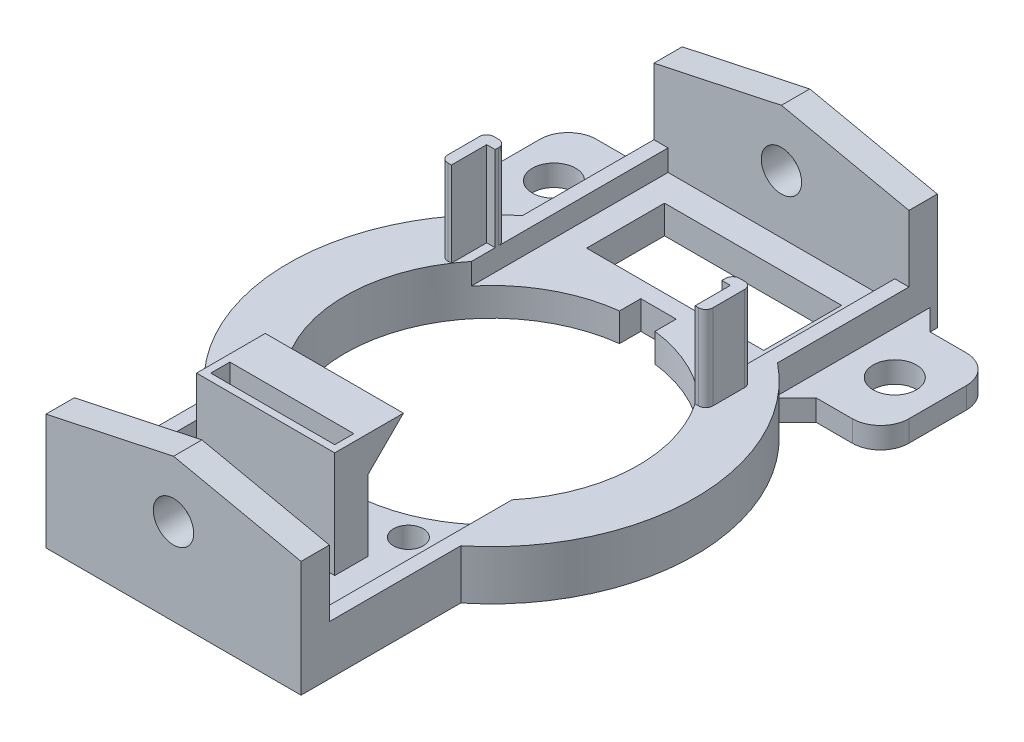
SolidWorks part; units mm, degrees
ref_plane "Front Plane" through (0, 0, 0) normal (0, 0, 1) x (1, 0, 0)
ref_plane "Top Plane" through (0, 0, 0) normal (0, 1, 0) x (1, 0, 0)
ref_plane "Right Plane" through (0, 0, 0) normal (1, 0, 0) x (0, 0, -1)
sketch "Sketch1" plane through (0, 0, 0) normal (0, 0, 1) x (1, 0, 0)
  line L3 (-18, 114.7896) -> (0, 114.7896)
  line L4 (0, 114.7896) -> (18, 114.7896)
  line L7 (0, 118.6383) -> (-38.0273, 110.5073) construction
  line L9 (38.0273, 110.5073) -> (0, 118.6383) construction
  line L11 (18, 114.7896) -> (18, 121.7896)
  line L12 (18, 121.7896) -> (16, 121.7896)
  line L13 (16, 121.7896) -> (16, 118.7896)
  line L14 (16, 118.7896) -> (-16, 118.7896)
  line L15 (-16, 118.7896) -> (-16, 121.7896)
  line L16 (-16, 121.7896) -> (-18, 121.7896)
  line L17 (-18, 121.7896) -> (-18, 114.7896)
  point P15 (0, 118.7896)
  dimension "D1" = 32
  dimension "D2" = 2
  dimension "D3" = 3
  dimension "D4" = 4
extrude "Boss-Extrude1" add sketch "Sketch1" along normal up to surface (89.8 mm away)
sketch "Sketch2" plane through (0, 114.7896, 0) normal (0, -1, 0) x (1, 0, 0)
  line L0 (18, 89.8) -> (18, 0) construction
  line L5 (-14, 54.9) -> (14, 54.9)
  line L6 (-14, 54.9) -> (-14, 34.9)
  line L7 (-14, 34.9) -> (14, 34.9)
  line L8 (14, 54.9) -> (14, 34.9)
  point P4 (0, 34.9)
  point P8 (18, 44.9)
  point P9 (14, 44.9)
  dimension "D1" = 4
  dimension "D2" = 20
extrude "Cut-Extrude1" [suppressed] cut sketch "Sketch2" against normal up to next
sketch "Sketch3" plane through (-18, 0, 0) normal (-1, 0, 0) x (0, 0, 1)
  line L0 (89.8, 121.7896) -> (0, 121.7896) construction
  line L1 (40.65, 118.7896) -> (49.15, 118.7896)
  line L2 (40.65, 118.7896) -> (40.65, 121.7896)
  line L3 (40.65, 121.7896) -> (49.15, 121.7896)
  line L4 (49.15, 118.7896) -> (49.15, 121.7896)
  line L5 (89.8, 118.7896) -> (0, 118.7896) construction
  point P9 (44.9, 121.7896)
  point P10 (44.9, 121.7896)
  dimension "D1" = 8.5
extrude "Cut-Extrude2" [suppressed] cut sketch "Sketch3" against normal through all
sketch "Sketch4" plane through (0, 118.7896, 0) normal (0, 1, 0) x (1, 0, 0)
  circle A0 centre (7.75, -23.25) radius 2.1 construction
  circle A4 centre (-7.75, -23.25) radius 2.1 construction
  circle A5 centre (7.75, -23.25) radius 2.1
  circle A6 centre (-7.75, -23.25) radius 2.1
extrude "Cut-Extrude3" [suppressed] cut sketch "Sketch4" against normal through all
ref_plane "Plane2" through (0, 0, 44.9) normal (0, 0, -1) x (-1, 0, 0)
sketch "Sketch5" plane through (0, 0, 0) normal (0, 0, 1) x (1, 0, 0)
  line L0 (-18, 114.7896) -> (-18, 131.1512)
  line L1 (-56.4, 122.9405) -> (0, 135) construction
  line L2 (-18, 131.1512) -> (0, 135)
  line L3 (0, 135) -> (18, 131.1512)
  line L4 (0, 135) -> (56.4, 122.9405) construction
  line L5 (18, 131.1512) -> (18, 114.7896)
  line L6 (18, 114.7896) -> (-18, 114.7896)
  line L7 (0.6273, 134.8659) -> (54.0273, 123.4479) construction
  line L8 (-54.0273, 123.4479) -> (-0.6273, 134.8659) construction
  circle A0 centre (0, 127) radius 2.85
  dimension "D1" = 5.7
  dimension "D2" = 8
extrude "Boss-Extrude2" add sketch "Sketch5" along normal blind 4
mirror "Mirror1" about plane through (0, 0, 44.9) normal (0, 0, -1) of "Boss-Extrude2"
sketch "Sketch6" plane through (0, 118.7896, 0) normal (0, 1, 0) x (1, 0, 0)
  line L1 (12.5, -19) -> (-12.5, -19)
  line L2 (12.5, -19) -> (12.5, -8)
  line L3 (12.5, -8) -> (-12.5, -8)
  line L4 (-12.5, -19) -> (-12.5, -8)
  point P4 (0, -8)
  dimension "D1" = 11
  dimension "D2" = 25
  dimension "D3" = 8
extrude "Cut-Extrude4" cut sketch "Sketch6" against normal through all
sketch "Sketch8" plane through (0, 118.7896, 0) normal (0, 1, 0) x (1, 0, 0)
  line L0 (16, -85.8) -> (-16, -85.8) construction
  line L1 (8.75, -75.8) -> (-8.75, -75.8)
  line L2 (8.75, -75.8) -> (8.75, -73.1)
  line L3 (8.75, -73.1) -> (-8.75, -73.1)
  line L4 (-8.75, -75.8) -> (-8.75, -73.1)
  line L5 (0, -89.8) -> (53.4, -89.8) construction
  line L6 (9.75, -72.1) -> (-9.75, -72.1)
  line L7 (-9.75, -76.8) -> (-9.75, -72.1)
  line L8 (9.75, -76.8) -> (-9.75, -76.8)
  line L9 (9.75, -76.8) -> (9.75, -72.1)
  point P6 (0, -85.8)
  point P7 (0, -75.8)
  dimension "D1" = 13
  dimension "D2" = 2.7
  dimension "D3" = 17.5
  dimension "D4" = 1
extrude "Boss-Extrude3" add sketch "Sketch8" along normal blind 15
sketch "Sketch9" plane through (-9.75, 0, 0) normal (-1, 0, 0) x (0, 0, 1)
  line L0 (72.1, 128.7896) -> (67.1, 133.7896)
  line L1 (72.1, 133.7896) -> (72.1, 118.7896) construction
  line L2 (67.1, 133.7896) -> (72.1, 133.7896)
  line L3 (72.1, 133.7896) -> (72.1, 128.7896)
  dimension "D1" = 5
  dimension "D2" = 45
extrude "Boss-Extrude4" add sketch "Sketch9" against normal up to surface (19.5 mm away) up to face at (9.75, 126.2896, 74.45)
sketch "Sketch13" plane through (0, 118.7896, 0) normal (0, 1, 0) x (1, 0, 0)
  line L4 (-8.75, -75.8) -> (8.75, -75.8)
  line L5 (8.75, -75.8) -> (8.75, -73.1)
  line L6 (8.75, -73.1) -> (-8.75, -73.1)
  line L7 (-8.75, -73.1) -> (-8.75, -75.8)
  line L8 (-8.75, -75.8) -> (8.75, -75.8)
  line L9 (8.75, -75.8) -> (8.75, -73.1)
  line L10 (8.75, -73.1) -> (-8.75, -73.1)
  line L11 (-8.75, -73.1) -> (-8.75, -75.8)
  dimension "D1" = 0
extrude "Cut-Extrude5" cut sketch "Sketch13" against normal through all
sketch "Sketch10" [suppressed] plane through (0, 121.7896, 0) normal (0, 1, 0) x (1, 0, 0)
  line L1 (16, -59.15) -> (18, -59.15)
  line L2 (16, -59.15) -> (16, -49.15)
  line L3 (16, -49.15) -> (18, -49.15)
  line L4 (18, -59.15) -> (18, -49.15)
  line L5 (0, -1000) -> (0, 49000) construction
  line L6 (-16, -49.15) -> (-18, -49.15)
  line L7 (-16, -59.15) -> (-16, -49.15)
  line L8 (-16, -59.15) -> (-18, -59.15)
  line L9 (-18, -59.15) -> (-18, -49.15)
  dimension "D1" = 10
extrude "Boss-Extrude5" [suppressed] add sketch "Sketch10" along normal up to surface (12 mm away)
sketch "Sketch14" plane through (0, 114.7896, 0) normal (0, 1, 0) x (1, 0, 0)
  line L0 (-18, -85.8) -> (-18, -4) construction
  line L1 (-18, -4) -> (-30.1, -4)
  line L2 (-18, -4) -> (-18, -20.1)
  line L3 (-18, -20.1) -> (-30.1, -20.1)
  line L4 (-30.1, -4) -> (-30.1, -20.1)
  circle A0 centre (-24.05, -12.05) radius 3.05
  point P9 (-30.1, -12.05)
  point P10 (-24.05, -20.1)
  dimension "D1" = 6.1
  dimension "D2" = 3
  dimension "D3" = 5
extrude "Boss-Extrude7" add sketch "Sketch14" along normal blind 3
mirror "Mirror2" about plane through (0, 0, 0) normal (1, 0, 0) of "Boss-Extrude7"
chamfer "Chamfer1" distance 3 angle 45 4 edges at (-18, 116.2896, 20.1) (-18, 116.2896, 4) (18, 116.2896, 4) (18, 116.2896, 20.1)
sketch "Sketch17" plane through (0, 118.7896, 0) normal (0, 1, 0) x (1, 0, 0)
  circle A0 centre (0, -81.15) radius 2.1
  circle A1 centre (0, -81.15) radius 2.85 construction
  dimension "D1" = 4.2
extrude "Cut-Extrude6" cut sketch "Sketch17" against normal through all
sketch "Sketch19" plane through (0, 114.7896, 0) normal (0, -1, 0) x (1, 0, 0)
  line L0 (18, 67.2537) -> (18, 55.122)
  line L2 (-16, 68.7262) -> (-16, 58.0335)
  line L3 (-18, 34.678) -> (-18, 22.5463)
  line L4 (18, 22.5463) -> (18, 34.678)
  line L6 (-18, 85.8) -> (-18, 4) construction
  line L7 (18, 85.8) -> (18, 4) construction
  line L8 (-16, 85.8) -> (-16, 4) construction
  arc A0 (-16, 58.0335) -> (-18, 34.678) centre (0, 44.9) ccw
  arc A1 (-16, 68.7262) -> (-18, 22.5463) centre (0, 44.9) ccw
  circle A2 centre (0, 44.9) radius 20.2 construction
  arc A3 (18, 22.5463) -> (18, 67.2537) centre (0, 44.9) ccw
  arc A4 (18, 34.678) -> (18, 55.122) centre (0, 44.9) ccw
  dimension "D1" = 0.5
  dimension "D2" = 8
extrude "Boss-Extrude8" add sketch "Sketch19" against normal up to surface (7 mm away) up to face at (-17, 121.7896, 44.9)
sketch "Sketch20" plane through (0, 114.7896, 0) normal (0, -1, 0) x (1, 0, 0)
  circle A0 centre (0, 44.9) radius 20.7
  arc A1 (18, 34.678) -> (18, 55.122) centre (0, 44.9) ccw construction
extrude "Cut-Extrude7" cut sketch "Sketch20" against normal up to next
fillet "Fillet1" radius 4 4 edges at (-30.1, 116.2896, 4) (-30.1, 116.2896, 20.1) (30.1, 116.2896, 4) (30.1, 116.2896, 20.1)
sketch "Sketch21" plane through (0, 118.7896, 0) normal (0, 1, 0) x (1, 0, 0)
  circle A0 centre (-10.2696, -66.9233) radius 2.1 construction
  circle A1 centre (10.2696, -66.9233) radius 2.1 construction
  circle A2 centre (-10.2696, -66.9233) radius 2.1
  circle A3 centre (10.2696, -66.9233) radius 2.1
extrude "Cut-Extrude8" cut sketch "Sketch21" against normal through all
sketch "Sketch22" plane through (0, 118.7896, 0) normal (0, 1, 0) x (1, 0, 0)
  line L0 (-1000, -44.9) -> (49000, -44.9) construction
  line L1 (-2.5, -65.4485) -> (2.5, -65.4485)
  line L2 (-2.5, -65.4485) -> (-2.5, -68.4485)
  line L3 (-2.5, -68.4485) -> (2.5, -68.4485)
  line L4 (2.5, -65.4485) -> (2.5, -68.4485)
  line L5 (2.5, -24.3515) -> (2.5, -21.3515)
  line L6 (-2.5, -21.3515) -> (2.5, -21.3515)
  line L7 (-2.5, -24.3515) -> (-2.5, -21.3515)
  line L8 (-2.5, -24.3515) -> (2.5, -24.3515)
  arc A0 (-16, -58.0335) -> (16, -58.0335) centre (0, -44.9) ccw construction
  dimension "D1" = 5
  dimension "D2" = 3
extrude "Cut-Extrude9" cut sketch "Sketch22" against normal through all
sketch "Sketch23" plane through (0, 121.7896, 0) normal (0, 1, 0) x (1, 0, 0)
  line L0 (-17, -33.3) -> (-17, -28.6) construction
  line L1 (-18.7, -26.9) -> (-16, -26.9)
  line L2 (-18.7, -26.9) -> (-18.7, -33.3826)
  line L3 (-18.7, -33.3826) -> (-17.2, -33.3826)
  line L4 (-17.2, -28.4) -> (-17.2, -33.3826)
  line L5 (-12.4996, -26.9) -> (-16, -26.9) construction
  line L6 (-12.4996, -26.9) -> (-12.4996, -28.4) construction
  line L7 (-12.4996, -28.4) -> (-16, -28.4) construction
  line L9 (-17, -28.6) -> (-14.5, -28.6) construction
  line L10 (-16, -31.7665) -> (-16, -4) construction
  line L11 (-16, -26.9) -> (-16, -28.4)
  line L12 (-16, -28.4) -> (-17.2, -28.4)
  arc A0 (-16, -31.7665) -> (-16, -58.0335) centre (0, -44.9) ccw construction
  arc A1 (-2.5, -24.3515) -> (-16, -31.7665) centre (0, -44.9) ccw construction
  point P4 (-14.9951, -27.7136)
  point P13 (-14.7214, -28.4)
  point P17 (-15.9414, -28.4)
  dimension "D1" = 0.2
  dimension "D2" = 0.2
  dimension "D3" = 1.5
  dimension "D4" = 1.5
extrude "Boss-Extrude9" add sketch "Sketch23" along normal up to surface (12 mm away)
fillet "Fillet2" radius 1 3 edges at (-18.7, 127.7896, 33.3826) (-16, 127.7896, 26.9) (-18.7, 127.7896, 26.9)
mirror "Mirror3" about plane through (0, 0, 0) normal (1, 0, 0) of "Fillet2", "Boss-Extrude9"
equation "\"width\"= 24"
equation "\"thk\"= 3"
equation "\"holesize\"= 4.2"
equation "\"holedistance\"= ( 20 + 12 ) / 2"
equation "\"threaded_hole\"= 3.9"
equation "\"fillet_radius\"= 2"
equation "\"ground_clearance\"= 25"
equation "\"tire_thk\"= 3"
equation "\"innerwheel_diam\" = \"wheel_diam\"-2*\"tire_thk\""
equation "\"innerwheel_thk\"= 8"
equation "\"wheel_diam\"= 2*(\"width\"/2+\"ground_clearance\")"
equation "\"coloursensor_holesize\"= 2.65"
equation "\"hole_to_edge\" = 4"
equation "\"D1@Sketch5\"=\"M4_insert_diam\""
equation "\"D1@Sketch17\"=\"holesize\""
equation "\"M4_insert_diam\"= 5.7"
